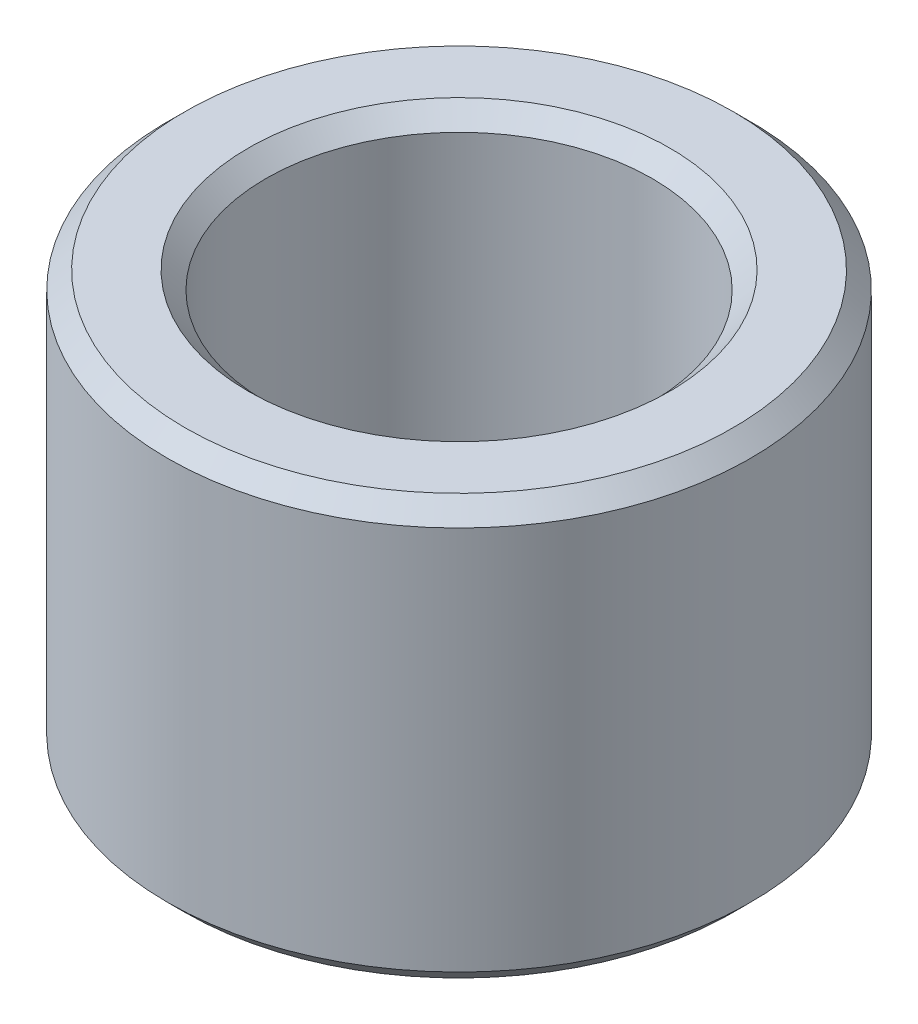
SolidWorks part; units mm, degrees
ref_plane "Front Plane" through (0, 0, 0) normal (0, 0, 1) x (1, 0, 0)
ref_plane "Top Plane" through (0, 0, 0) normal (0, 1, 0) x (1, 0, 0)
ref_plane "Right Plane" through (0, 0, 0) normal (1, 0, 0) x (0, 0, -1)
sketch "Sketch1" plane through (0, 0, 0) normal (0, 1, 0) x (1, 0, 0)
  circle A0 centre (0, 0) radius 15
  dimension "SLEEVE_OD" = 30
extrude "Boss-Extrude1" add sketch "Sketch1" along normal blind 21.5945
sketch "Sketch2" plane through (0, 0, 0) normal (0, 1, 0) x (1, 0, 0)
  circle A0 centre (0, 0) radius 9.9368
  dimension "BORE_D" = 19.8735
extrude "Cut-Extrude1" cut sketch "Sketch2" along normal through all
chamfer "Chamfer1" distance 0.9055 angle 45 4 edges at (0, 21.5945, 9.9368) (0, 0, 9.9368) (0, 0, 15) (0, 21.5945, 15)
